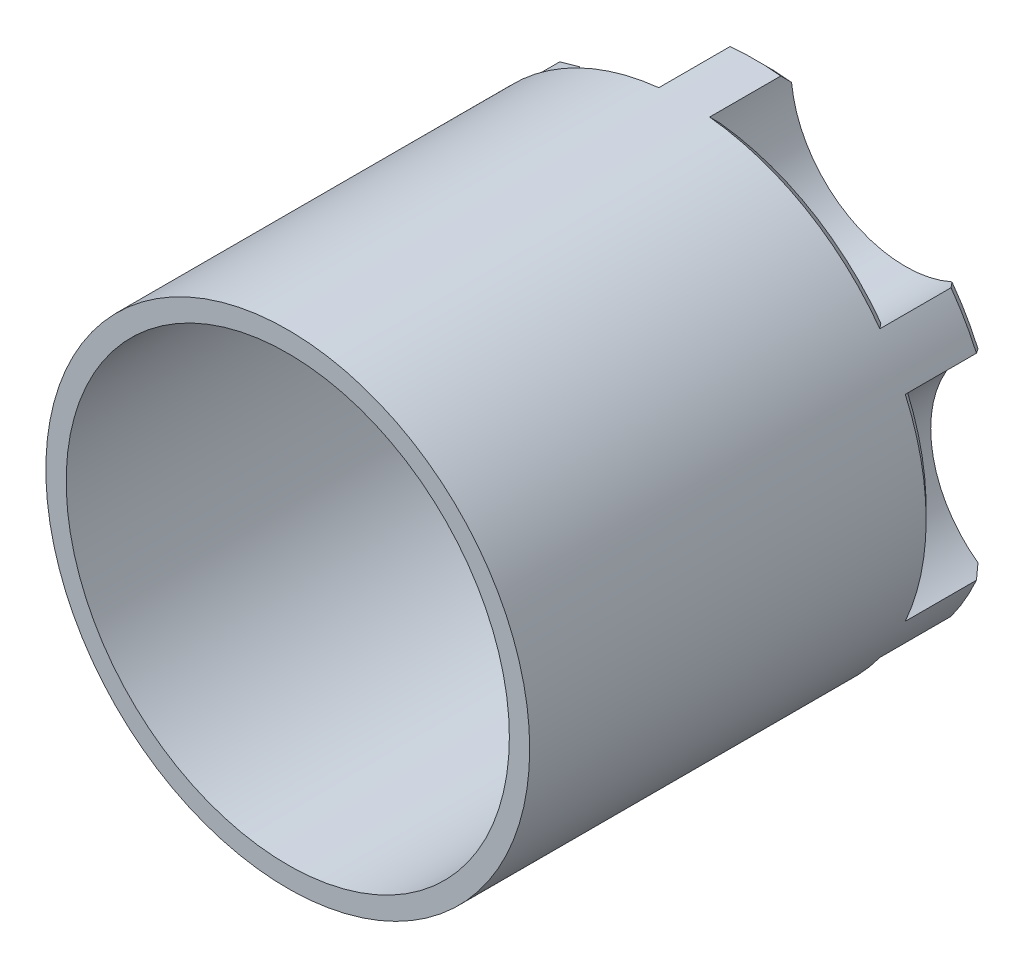
SolidWorks part; units mm, degrees
ref_plane "Front Plane" through (0, 0, 0) normal (0, 0, 1) x (1, 0, 0)
ref_plane "Top Plane" through (0, 0, 0) normal (0, 1, 0) x (1, 0, 0)
ref_plane "Right Plane" through (0, 0, 0) normal (1, 0, 0) x (0, 0, -1)
sketch "Sketch1" plane through (0, 0, 0) normal (0, 0, 1) x (1, 0, 0)
  line L0 (-1.4524, 0) -> (71.008, 0) construction
  line L1 (0, 0) -> (0, 72.303) construction
  circle A1 centre (0, 0) radius 23.8
  circle A2 centre (0, 0) radius 21.8
  arc A3 (21.7478, 9.6682) -> (21.7478, -9.6682) centre (27.5, 0) ccw
  arc A4 (19.1987, 10.3272) -> (19.1987, -10.3272) centre (27.5, 0) ccw
  circle A5 centre (27.5, 0) radius 13.25 construction
  circle A6 centre (27.5, 0) radius 11.25 construction
  arc A7 (18.5429, -11.463) -> (0.6557, -21.7901) centre (13.75, -23.8157) ccw
  arc A8 (19.2468, -14) -> (2.501, -23.6682) centre (13.75, -23.8157) ccw
  arc A9 (-0.6557, -21.7901) -> (-18.5429, -11.463) centre (-13.75, -23.8157) ccw
  arc A10 (-2.501, -23.6682) -> (-19.2468, -14) centre (-13.75, -23.8157) ccw
  arc A11 (-19.1987, -10.3272) -> (-19.1987, 10.3272) centre (-27.5, 0) ccw
  arc A12 (-21.7478, -9.6682) -> (-21.7478, 9.6682) centre (-27.5, 0) ccw
  arc A13 (-18.5429, 11.463) -> (-0.6557, 21.7901) centre (-13.75, 23.8157) ccw
  arc A14 (-19.2468, 14) -> (-2.501, 23.6682) centre (-13.75, 23.8157) ccw
  arc A15 (0.6557, 21.7901) -> (18.5429, 11.463) centre (13.75, 23.8157) ccw
  arc A16 (2.501, 23.6682) -> (19.2468, 14) centre (13.75, 23.8157) ccw
  arc A17 (16.724, 17.2136) -> (6.5455, 23.0902) centre (0, 0) ccw construction
  point P50 (0, 0)
  dimension "D2" = 22.5
  dimension "D6" = 0.2
  dimension "D1" = 2
  dimension "D3" = 27.5
  dimension "D4" = 2
  dimension "D5" = 6
extrude "Boss-Extrude1" add sketch "Sketch1" along normal blind 3 and the other way blind 37 contours A1 A14 A2 | A1 A16 A2 | A16 A1 A14 A2 | A16 A2 A3 A1 | A1 A3 A2 | A1 A8 A2 | A8 A1 A3 A2 | A10 A1 A8 A2 | A2 A10 A1 | A12 A1 A10 A2 | A2 A12 A1 | A14 A1 A12 A2 region at (22.1865, 0, 0) region at (19.691, 11.3686, 0) region at (19.691, -11.3686, 0) region at (11.0932, 19.214, 0) region at (11.0932, -19.214, 0) region at (0, 22.7372, 0) region at (0, -22.7372, 0) region at (-11.0932, 19.214, 0) region at (-11.0932, -19.214, 0) region at (-19.691, 11.3686, 0) region at (-19.691, -11.3686, 0) region at (-22.1865, 0, 0)
extrude "Boss-Extrude2" add sketch "Sketch1<5>" along normal blind 2 from surface contours A2 A16 | A2 A14 | A2 A12 | A2 A10 | A2 A8 | A2 A3 | A14 A2 A13 | A16 A1 A14 A2 | A14 A1 A12 A2 | A12 A2 A11 | A12 A1 A10 A2 | A10 A2 A9 | A10 A1 A8 A2 | A8 A2 A7 | A8 A1 A3 A2 | A2 A4 A3 | A16 A2 A3 A1 | A16 A2 A15 region at (19.691, 11.3686, 0) region at (19.691, -11.3686, 0) region at (16.0354, 0, 0) region at (19.2066, 0, 0) region at (0, 22.7372, 0) region at (9.6033, 16.6334, 0) region at (17.8051, 12.2088, 0) region at (0, -22.7372, 0) region at (8.0194, -13.89, 0) region at (9.6033, -16.6334, 0) region at (-19.691, 11.3686, 0) region at (-9.6033, 16.6334, 0) region at (-1.6706, 21.5241, 0) region at (-19.691, -11.3686, 0) region at (-8.0194, -13.89, 0) region at (-9.6033, -16.6334, 0) region at (-19.2066, 0, 0) region at (-19.4726, 9.3138, 0) starting at face at (23.8, 0, -37)
sketch "Sketch1<5>" plane through (0, 0, 0) normal (0, 0, 1) x (1, 0, 0) same geometry as "Sketch1"
extrude "Boss-Extrude4" add sketch "Sketch1<7>" against normal blind 5 from surface contours A14 A2 A13 | A14 A1 A12 A2 | A12 A2 A11 | A12 A1 A10 A2 | A10 A2 A9 | A10 A1 A8 A2 | A8 A2 A7 | A8 A1 A3 A2 | A2 A4 A3 | A16 A2 A3 A1 | A16 A2 A15 | A16 A1 A14 A2 region at (19.691, 11.3686, 0) region at (19.691, -11.3686, 0) region at (16.0354, 0, 0) region at (0, 22.7372, 0) region at (17.8051, 12.2088, 0) region at (0, -22.7372, 0) region at (8.0194, -13.89, 0) region at (-19.691, 11.3686, 0) region at (-1.6706, 21.5241, 0) region at (-19.691, -11.3686, 0) region at (-8.0194, -13.89, 0) region at (-19.4726, 9.3138, 0) starting at face at (0, 0, -37)
sketch "Sketch1<7>" plane through (0, 0, 0) normal (0, 0, 1) x (1, 0, 0) same geometry as "Sketch1"
extrude "Boss-Extrude5" add sketch "Sketch1<8>" against normal blind 2 from surface contours A14 A2 A13 | A16 A1 A14 A2 | A16 A2 A15 | A15 A2 A13 A11 A9 A7 A4 | A2 A4 A3 | A16 A2 A3 A1 | A8 A1 A3 A2 | A8 A2 A7 | A10 A1 A8 A2 | A10 A2 A9 | A12 A1 A10 A2 | A12 A2 A11 | A14 A1 A12 A2 region at (19.691, 11.3686, 0) region at (19.691, -11.3686, 0) region at (16.0354, 0, 0) region at (0, 22.7372, 0) region at (17.8051, 12.2088, 0) region at (0, 0, 0) region at (0, -22.7372, 0) region at (8.0194, -13.89, 0) region at (-19.691, 11.3686, 0) region at (-1.6706, 21.5241, 0) region at (-19.691, -11.3686, 0) region at (-8.0194, -13.89, 0) region at (-19.4726, 9.3138, 0) starting at face at (0, 0, -42)
sketch "Sketch1<8>" plane through (0, 0, 0) normal (0, 0, 1) x (1, 0, 0) same geometry as "Sketch1"
chamfer "Chamfer1" distance 1 angle 45 12 edges at (-20.6114, 11.9, -44) (-20.6114, -11.9, -44) (0, -23.8, -44) (20.6114, -11.9, -44) (20.6114, 11.9, -44) (0, 23.8, -44) (23.8, 0, -37) (11.9, -20.6114, -37) (-11.9, -20.6114, -37) (-23.8, 0, -37) (-11.9, 20.6114, -37) (11.9, 20.6114, -37)
